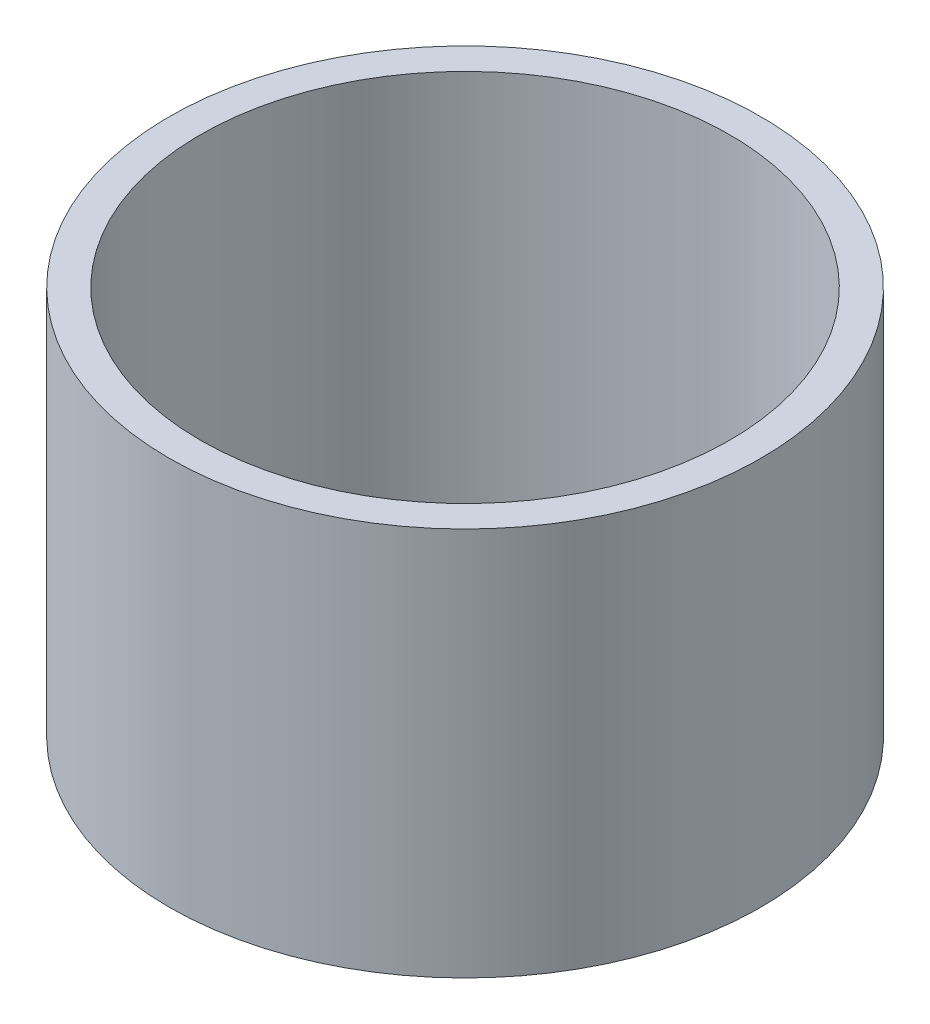
SolidWorks part; units mm, degrees
ref_plane "Front Plane" through (0, 0, 0) normal (0, 0, 1) x (1, 0, 0)
ref_plane "Top Plane" through (0, 0, 0) normal (0, 1, 0) x (1, 0, 0)
ref_plane "Right Plane" through (0, 0, 0) normal (1, 0, 0) x (0, 0, -1)
sketch "Sketch1" plane through (0, 0, 0) normal (0, 1, 0) x (1, 0, 0)
  circle A0 centre (0, 0) radius 35
  dimension "SLEEVE_OD" = 70
extrude "Boss-Extrude1" add sketch "Sketch1" along normal blind 45.9991
sketch "Sketch2" plane through (0, 0, 0) normal (0, 1, 0) x (1, 0, 0)
  circle A0 centre (0, 0) radius 31.3101
  dimension "BORE_D" = 62.6202
extrude "Cut-Extrude1" cut sketch "Sketch2" along normal through all
chamfer "Chamfer1" distance 1.7483 angle 60 rebuild error yes
